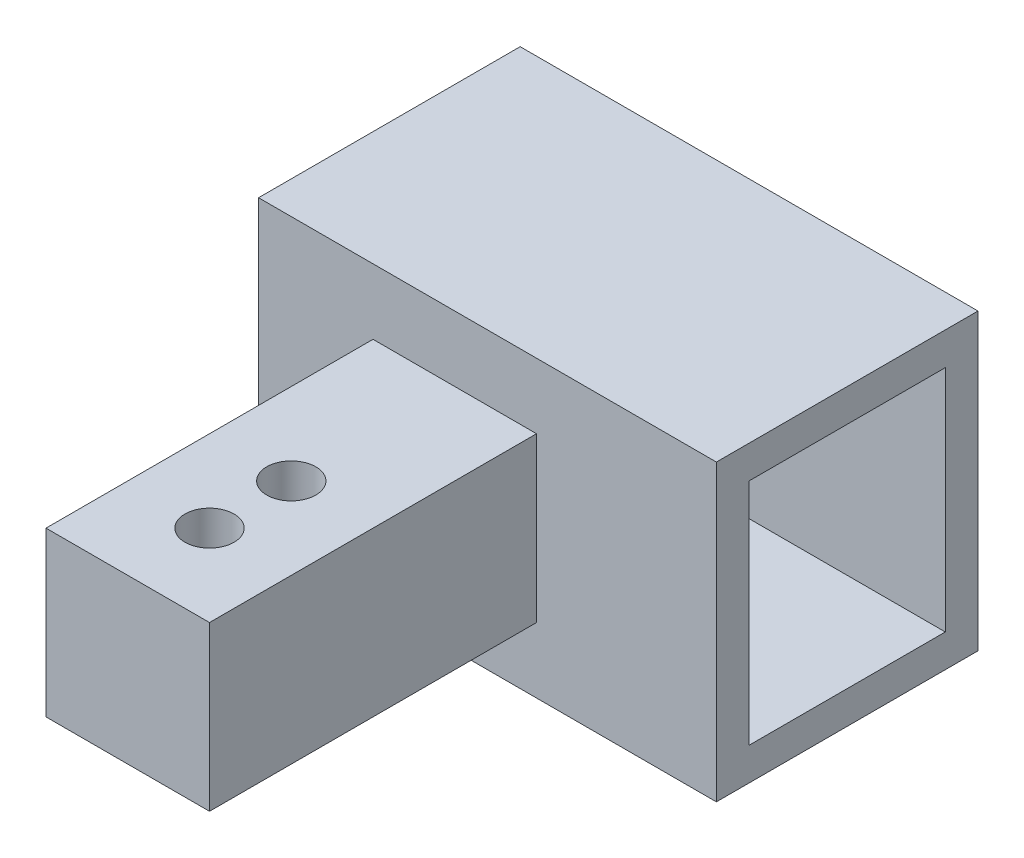
SolidWorks part; units mm, degrees
ref_plane "Front Plane" through (0, 0, 0) normal (0, 0, 1) x (1, 0, 0)
ref_plane "Top Plane" through (0, 0, 0) normal (0, 1, 0) x (1, 0, 0)
ref_plane "Right Plane" through (0, 0, 0) normal (1, 0, 0) x (0, 0, -1)
sketch "Sketch1" plane through (0, 0, 0) normal (0, 1, 0) x (1, 0, 0)
  line L1 (-13.5385, 5.3538) -> (14.4615, 5.3538)
  line L2 (-13.5385, 5.3538) -> (-13.5385, -10.6462)
  line L3 (-13.5385, -10.6462) -> (14.4615, -10.6462)
  line L4 (14.4615, 5.3538) -> (14.4615, -10.6462)
  dimension "D1" = 16
  dimension "D2" = 28
extrude "Boss-Extrude1" add sketch "Sketch1" along normal blind 18
sketch "Sketch3" plane through (0, 0, 10.6462) normal (0, 0, 1) x (1, 0, 0)
  line L0 (-13.5385, 18) -> (14.4615, 18) construction
  line L1 (-6.5385, 14) -> (3.4615, 14)
  line L2 (-6.5385, 14) -> (-6.5385, 4)
  line L3 (-6.5385, 4) -> (3.4615, 4)
  line L4 (3.4615, 14) -> (3.4615, 4)
  line L5 (-13.5385, 0) -> (14.4615, 0) construction
  line L6 (14.4615, 18) -> (14.4615, 0) construction
  point P8 (14.4615, 9)
  dimension "D1" = 10
  dimension "D2" = 10
  dimension "D3" = 4
  dimension "D4" = 14
  dimension "D5" = 11
extrude "Boss-Extrude2" add sketch "Sketch3" along normal blind 20
sketch "Sketch4" plane through (14.4615, 0, 0) normal (1, 0, 0) x (0, 0, -1)
  line L0 (-10.6462, 18) -> (5.3538, 18) construction
  line L1 (-8.6462, 16) -> (3.3538, 16)
  line L2 (-8.6462, 16) -> (-8.6462, 2)
  line L3 (-8.6462, 2) -> (3.3538, 2)
  line L4 (3.3538, 16) -> (3.3538, 2)
  line L5 (5.3538, 18) -> (5.3538, 0) construction
  line L6 (-10.6462, 0) -> (5.3538, 0) construction
  line L7 (-10.6462, 18) -> (-10.6462, 0) construction
  dimension "D1" = 2
  dimension "D2" = 2
  dimension "D3" = 2
  dimension "D4" = 2
extrude "Cut-Extrude1" cut sketch "Sketch4" against normal blind 25
sketch "Sketch5" plane through (0, 14, 0) normal (0, 1, 0) x (1, 0, 0)
  line L0 (3.4615, -10.6462) -> (-6.5385, -10.6462) construction
  line L1 (3.4615, -30.6462) -> (-6.5385, -30.6462) construction
  line L2 (-6.5385, -30.6462) -> (-6.5385, -10.6462) construction
  circle A0 centre (-1.5385, -20.6462) radius 1.5
  circle A1 centre (-1.5385, -25.6462) radius 1.5
  dimension "D1" = 3
  dimension "D2" = 3
  dimension "D5" = 5
  dimension "D6" = 5
  dimension "D3" = 10
  dimension "D4" = 5
extrude "Cut-Extrude2" cut sketch "Sketch5" against normal blind 25
extrude "Cut-Extrude3" cut sketch "Sketch4<2>" against normal blind 26
sketch "Sketch4<2>" plane through (14.4615, 0, 0) normal (1, 0, 0) x (0, 0, -1) same geometry as "Sketch4"
